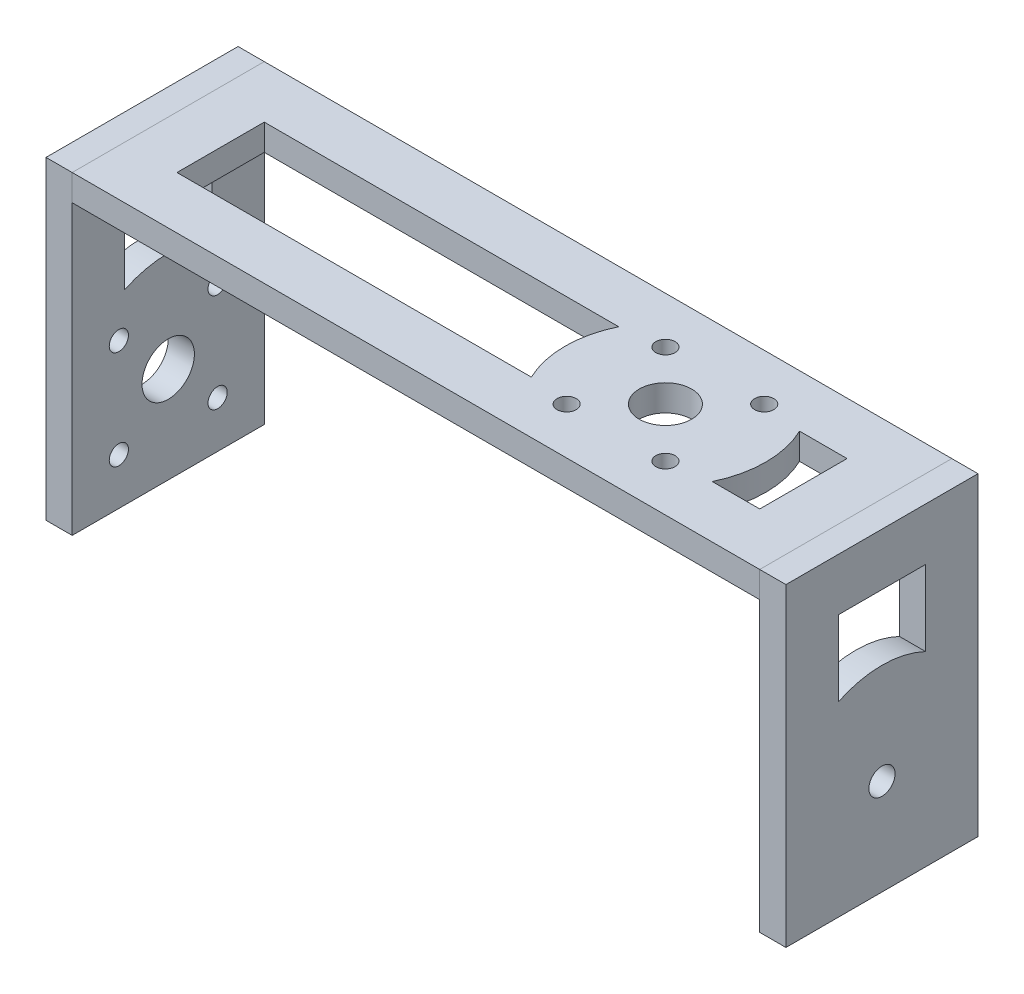
SolidWorks part; units mm, degrees
ref_plane "Front Plane" through (0, 0, 0) normal (0, 0, 1) x (1, 0, 0)
ref_plane "Top Plane" through (0, 0, 0) normal (0, 1, 0) x (1, 0, 0)
ref_plane "Right Plane" through (0, 0, 0) normal (1, 0, 0) x (0, 0, -1)
sketch "Sketch1" plane through (0, 0, 0) normal (0, 1, 0) x (1, 0, 0)
  line L0 (17.575, 0) -> (19.6963, 2.1213) construction
  line L1 (39.375, 11) -> (-39.375, 11)
  line L2 (39.375, 11) -> (39.375, -11)
  line L3 (39.375, -11) -> (-39.375, -11)
  line L4 (-39.375, 11) -> (-39.375, -11)
  line L5 (39.375, 11) -> (-39.375, -11) construction
  line L6 (39.375, -11) -> (-39.375, 11) construction
  line L7 (-39.375, 11) -> (-42.375, 11)
  line L8 (-39.375, 11) -> (-39.375, -11)
  line L9 (-39.375, -11) -> (-42.375, -11)
  line L10 (-42.375, 11) -> (-42.375, -11)
  line L11 (39.375, 11) -> (42.375, 11)
  line L12 (39.375, 11) -> (39.375, -11)
  line L13 (39.375, -11) -> (42.375, -11)
  line L14 (42.375, 11) -> (42.375, -11)
  line L15 (-33.375, 5) -> (-33.375, 11) construction
  line L16 (33.375, 5) -> (27.9312, 5)
  line L17 (33.375, 5) -> (33.375, -5)
  line L18 (33.375, -5) -> (27.9312, -5)
  line L19 (-33.375, 5) -> (-33.375, -5)
  line L20 (33.375, 5) -> (-33.375, -5) construction
  line L21 (33.375, -5) -> (-33.375, 5) construction
  line L22 (-33.375, 5) -> (-39.375, 5) construction
  line L23 (7.2188, 5) -> (-33.375, 5)
  line L24 (7.2188, -5) -> (-33.375, -5)
  circle A0 centre (17.575, 0) radius 3
  arc A1 (7.2188, 5) -> (7.2188, -5) centre (17.575, 0) ccw
  arc A2 (27.9312, -5) -> (27.9312, 5) centre (17.575, 0) ccw
  point P0 (0, 0)
  point P13 (0, 0)
  dimension "D5" = 6
  dimension "D8" = 23
  dimension "D1" = 78.75
  dimension "D2" = 22
  dimension "D3" = 3
  dimension "D4" = 21.8
  dimension "D6" = 45
  dimension "D7" = 6
extrude "Boss-Extrude1" add sketch "Sketch1" against normal blind 3 contours L1 L4 L3 L2 region at (38.5573, 0, 0)
extrude "Boss-Extrude2" add sketch "Sketch1<3>" against normal blind 36 separate body contours L7 L10 L9 L4 | L14 L11 L2 L13 region at (40.875, 0, 0) region at (-40.875, 0, 0)
sketch "Sketch1<3>" plane through (0, 0, 0) normal (0, 1, 0) x (1, 0, 0) same geometry as "Sketch1"
sketch "Sketch2" plane through (-42.375, 0, 0) normal (-1, 0, 0) x (0, 0, 1)
  line L0 (0, -25) -> (5.6569, -19.3431) construction
  line L1 (-11, -36) -> (11, -36) construction
  circle A0 centre (0, -25) radius 3
  circle A1 centre (5.6569, -19.3431) radius 1.1
  dimension "D1" = 6
  dimension "D5" = 2.2
  dimension "D2" = 11
  dimension "D3" = 8
  dimension "D4" = 45
extrude "Cut-Extrude1" cut sketch "Sketch2" against normal up to surface (3 mm away) contours A0 | A1 region at (-42.375, -25, 0) up to face at (-39.375, -18, 0)
sketch "Sketch3" plane through (42.375, 0, 0) normal (1, 0, 0) x (0, 0, -1)
  circle A0 centre (0, -25) radius 1.5
  dimension "D1" = 3
extrude "Cut-Extrude2" cut sketch "Sketch3" against normal up to surface (3 mm away) up to face at (39.375, -18, 0)
pattern_circular "CirPattern1" count 4 over 360 about axis through (39.375, -25, 0) along (1, 0, 0) of "Cut-Extrude1"
sketch "Sketch4" plane through (0, 0, 0) normal (0, 1, 0) x (1, 0, 0)
  line L0 (23.2319, 5.6569) -> (17.575, 0) construction
  line L1 (39.375, 11) -> (-39.375, 11) construction
  circle A0 centre (23.2319, 5.6569) radius 1.1
  dimension "D3" = 2.2
  dimension "D1" = 45
  dimension "D2" = 8
extrude "Cut-Extrude3" cut sketch "Sketch4" against normal up to surface (3 mm away) up to face at (17.575, -3, 3)
pattern_circular "CirPattern2" count 4 over 360 about axis through (17.575, 0, 0) along (0, 1, 0) of "Cut-Extrude3"
sketch "Sketch5" plane through (-42.375, 0, 0) normal (-1, 0, 0) x (0, 0, 1)
  line L0 (-11, -6) -> (-5, -6) construction
  line L2 (-5, -14.6438) -> (-5, -6)
  line L3 (-5, -6) -> (5, -6)
  line L4 (5, -14.6438) -> (5, -6)
  line L5 (-11, -36) -> (-11, 0) construction
  line L6 (-5, -6) -> (-5, 0) construction
  line L7 (12.1, 0) -> (-12.1, 0) construction
  line L8 (5, -6) -> (11, -6) construction
  line L9 (11, -36) -> (11, 0) construction
  arc A0 (5, -14.6438) -> (-5, -14.6438) centre (0, -25) ccw
  dimension "D2" = 23
  dimension "D1" = 6
extrude "Cut-Extrude4" cut sketch "Sketch5" against normal up to surface (84.75 mm away) up to face at (42.375, -25, -1.5)
